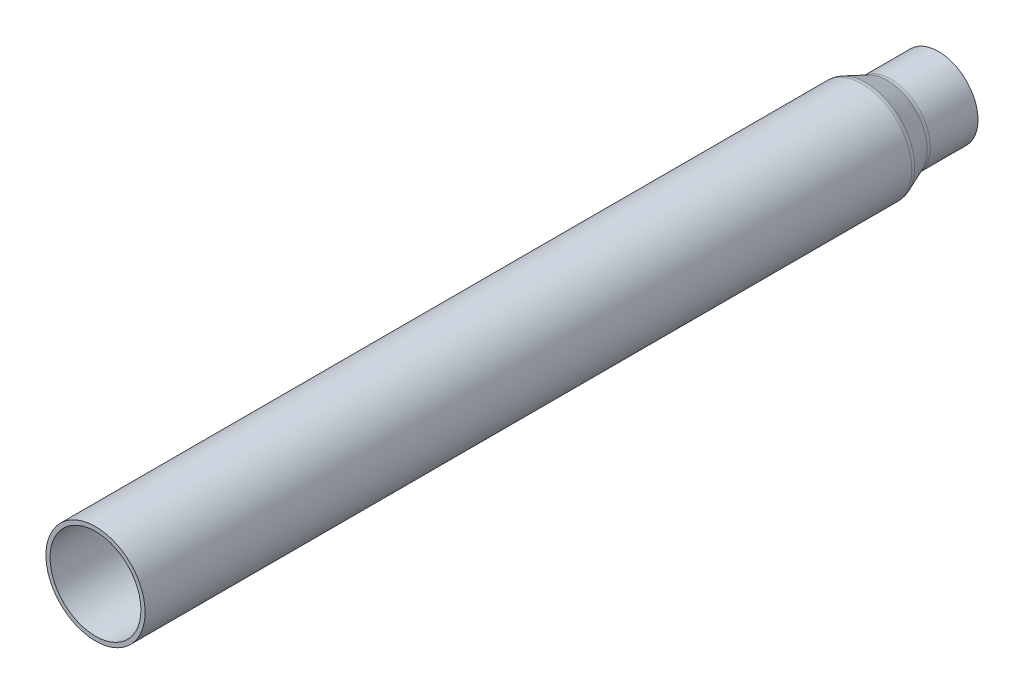
SolidWorks part; units mm, degrees
ref_plane "Front Plane" through (0, 0, 0) normal (0, 0, 1) x (1, 0, 0)
ref_plane "Top Plane" through (0, 0, 0) normal (0, 1, 0) x (1, 0, 0)
ref_plane "Right Plane" through (0, 0, 0) normal (1, 0, 0) x (0, 0, -1)
sketch "Sketch1" plane through (0, 0, 0) normal (0, 1, 0) x (1, 0, 0)
  line L0 (10.1092, 50.8) -> (10.1092, 38.1)
  line L1 (10.1092, 38.1) -> (12.7, 31.75)
  line L2 (12.7, 31.75) -> (12.7, -165.1)
  line L3 (12.7, -165.1) -> (11.6332, -165.1)
  line L4 (11.6332, -165.1) -> (11.6332, 31.75)
  line L5 (11.6332, 31.75) -> (9.0424, 38.1)
  line L6 (9.0424, 38.1) -> (9.0424, 50.8)
  line L7 (9.0424, 50.8) -> (10.1092, 50.8)
  line L8 (0, 0) -> (0, 39700.89) construction
  point P11 (9.0424, 44.826)
  point P12 (0, 0)
  dimension "D1" = 1.0668
  dimension "D2" = 25.4
  dimension "D3" = 18.0848
  dimension "D4" = 12.7
  dimension "D5" = 6.35
  dimension "D6" = 215.9
  dimension "D7" = 50.8
revolve "Revolve1" add sketch "Sketch1" angle 360 about L8
fillet "Fillet1" radius 2.54 4 edges at (9.0424, 0, -38.1) (10.1092, 0, -38.1) (11.6332, 0, -31.75) (12.7, 0, -31.75)
